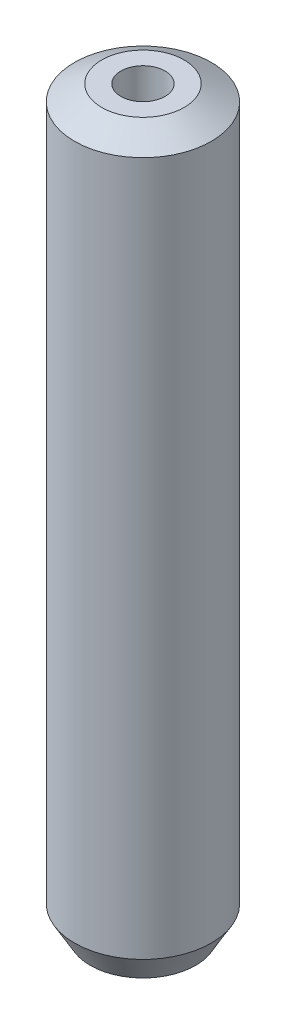
SolidWorks part; units mm, degrees
ref_plane "Front Plane" through (0, 0, 0) normal (0, 0, 1) x (1, 0, 0)
ref_plane "Top Plane" through (0, 0, 0) normal (0, 1, 0) x (1, 0, 0)
ref_plane "Right Plane" through (0, 0, 0) normal (1, 0, 0) x (0, 0, -1)
sketch "Sketch1" plane through (0, 0, 0) normal (0, 1, 0) x (1, 0, 0)
  circle A0 centre (0, 0) radius 5
  dimension "SHAFT_OD" = 10
extrude "Boss-Extrude1" add sketch "Sketch1" along normal blind 53.8897
sketch "Sketch2" plane through (0, 0, 0) normal (0, 1, 0) x (1, 0, 0)
  circle A0 centre (0, 0) radius 1.6135
  dimension "BORE_D" = 3.227
extrude "Cut-Extrude1" cut sketch "Sketch2" along normal through all
chamfer "Chamfer1" distance 1.1482 angle 60 2 edges at (0, 53.8897, 5) (0, 0, 5) first distance on face at (0, 53.8897, 5) first distance on face at (0, 0, 1.6135)
